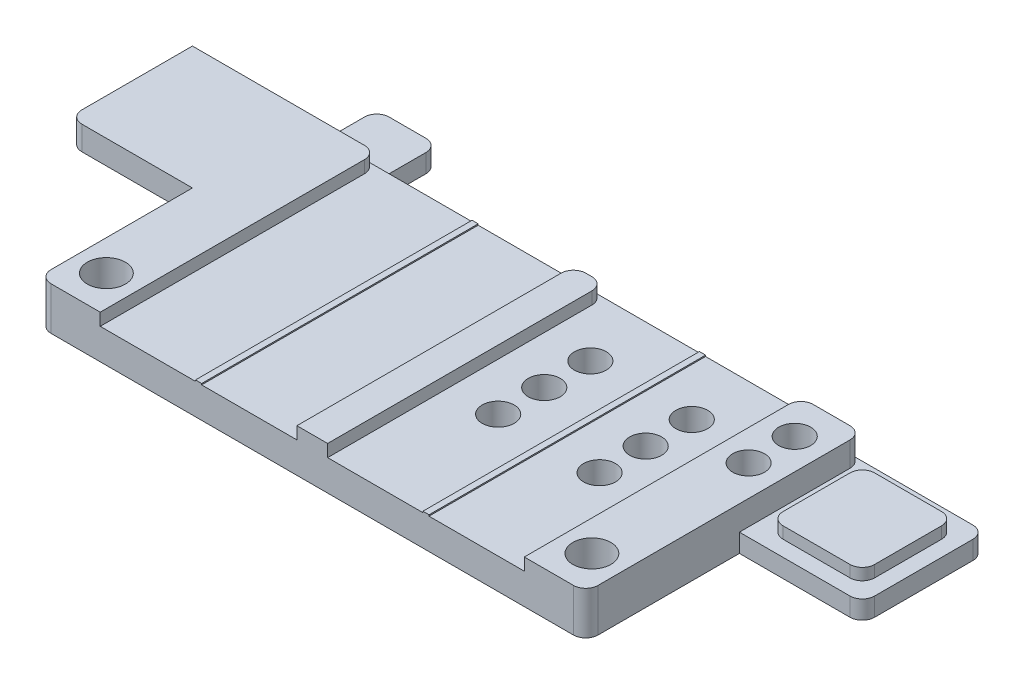
SolidWorks part; units mm, degrees
note: The reader was unsure of these and kept them because the rebuilt part matched: shared geometry of "Sketch1<3>", "Sketch1<4>", "Sketch5<3>", "Sketch5<4>", "Sketch5<5>".
ref_plane "Front Plane" through (0, 0, 0) normal (0, 0, 1) x (1, 0, 0)
ref_plane "Top Plane" through (0, 0, 0) normal (0, 1, 0) x (1, 0, 0)
ref_plane "Right Plane" through (0, 0, 0) normal (1, 0, 0) x (0, 0, -1)
sketch "Sketch1" plane through (0, 0, 0) normal (0, 1, 0) x (1, 0, 0)
  line L0 (0, 108.5954) -> (0, -94.6715) construction
  line L1 (-125.0313, 0) -> (305.9503, 0) construction
  line L10 (134.5, 0) -> (134.5, 45)
  line L11 (134.5, 45) -> (119, 45)
  line L12 (119, 45) -> (119, 0)
  line L13 (119, 0) -> (134.5, 0)
  line L14 (119, 45) -> (118, 45)
  line L15 (118, 45) -> (118, 0)
  line L16 (118, 0) -> (119, 0)
  line L18 (118, 45) -> (102.5, 45)
  line L22 (100, 108.5954) -> (100, 0) construction
  line L23 (102.5, 45) -> (102.5, 0)
  line L24 (102.5, 0) -> (118, 0)
  line L25 (102.5, 45) -> (97.5, 45)
  line L26 (97.5, 45) -> (97.5, 0)
  line L27 (97.5, 0) -> (102.5, 0)
  line L28 (97.5, 45) -> (82, 45)
  line L29 (82, 45) -> (82, 0)
  line L30 (82, 0) -> (97.5, 0)
  line L31 (82, 45) -> (81, 45)
  line L32 (81, 45) -> (81, 0)
  line L33 (81, 0) -> (82, 0)
  line L34 (81, 45) -> (65.5, 45)
  line L35 (65.5, 45) -> (65.5, 0)
  line L36 (65.5, 0) -> (81, 0)
  line L37 (134.5, 45) -> (144.5, 45)
  line L38 (144.5, 45) -> (144.5, 0)
  line L39 (144.5, 0) -> (134.5, 0)
  line L40 (65.5, 45) -> (55.5, 45)
  line L41 (55.5, 45) -> (55.5, 0)
  line L42 (55.5, 0) -> (65.5, 0)
  circle A10 centre (110.25, 35) radius 2.6
  circle A11 centre (110.25, 27.5) radius 2.6
  circle A12 centre (110.25, 20) radius 2.6
  circle A13 centre (126.75, 35) radius 2.6
  circle A14 centre (126.75, 27.5) radius 2.6
  circle A15 centre (126.75, 20) radius 2.6
  circle A16 centre (139.5, 39) radius 2.6
  circle A17 centre (139.5, 31.5) radius 2.6
  point P7 (100, 45)
  point P38 (110.25, 45)
  point P44 (126.75, 45)
  point P46 (139.5, 45)
  dimension "D6" = 5
  dimension "D7" = 15.5
  dimension "D8" = 1
  dimension "D9" = 15.5
  dimension "D12" = 7.5
  dimension "D14" = 10
  dimension "D10" = 5.2
  dimension "D13" = 7.5
  dimension "D15" = 7.5
  dimension "D16" = 10
  dimension "D2" = 45
  dimension "D3" = 15.5
  dimension "D4" = 1
  dimension "D5" = 15.5
  dimension "D11" = 100
  dimension "D17" = 6
  dimension "D18" = 10
extrude "Boss-Extrude1" add sketch "Sketch1" along normal blind 5 contours L35 L36 L32 L34 | L29 L30 L26 L28 | L23 L24 L15 L18 A12 A11 A10 | L12 L13 L10 L11 A15 A14 A13
extrude "Boss-Extrude2" add sketch "Sketch1<3>" along normal blind 5.2 contours L32 L33 L29 L31 | L15 L16 L12 L14
sketch "Sketch1<3>" plane through (0, 0, 0) normal (0, 1, 0) x (1, 0, 0) same geometry as "Sketch1"
extrude "Boss-Extrude3" add sketch "Sketch1<4>" along normal blind 7 contours L26 L27 L23 L25 | L39 L38 L37 L10 A17 A16 | L41 L42 L35 L40
sketch "Sketch1<4>" plane through (0, 0, 0) normal (0, 1, 0) x (1, 0, 0) same geometry as "Sketch1"
sketch "Sketch2" plane through (0, 0, 0) normal (0, -1, 0) x (-1, 0, 0)
  line L0 (-139.5, 31.5) -> (-139.5, 39) construction
  line L1 (-135.75, 42.75) -> (-143.25, 42.75)
  line L2 (-135.75, 42.75) -> (-135.75, 27.75)
  line L3 (-135.75, 27.75) -> (-143.25, 27.75)
  line L4 (-143.25, 42.75) -> (-143.25, 27.75)
  line L5 (-135.75, 42.75) -> (-143.25, 27.75) construction
  line L6 (-135.75, 27.75) -> (-143.25, 42.75) construction
  point P0 (-139.5, 35.25)
  dimension "D1" = 7.5
  dimension "D2" = 15
extrude "Cut-Extrude1" cut sketch "Sketch2" against normal blind 1.1
sketch "Sketch3" plane through (0, 7, 0) normal (0, 1, 0) x (1, 0, 0)
  line L0 (100, 49.6455) -> (100, -11.2034) construction
  line L2 (55.5, 0) -> (65.5, 0) construction
  line L3 (55.5, 45) -> (55.5, 0) construction
  circle A0 centre (60.5, 6) radius 3.1
  circle A1 centre (139.5, 6) radius 3.1
  point P9 (60.5, 0)
  dimension "D1" = 6.2
  dimension "D2" = 6
  dimension "D3" = 5
  dimension "D4" = 39.5
extrude "Cut-Extrude2" cut sketch "Sketch3" against normal through all
sketch "Sketch5" plane through (0, 0, 0) normal (0, 1, 0) x (1, 0, 0)
  line L0 (144.5, 25) -> (164.5, 25)
  line L1 (144.5, 45) -> (144.5, 0) construction
  line L2 (164.5, 25) -> (164.5, 45)
  line L3 (164.5, 45) -> (144.5, 45)
  line L4 (144.5, 45) -> (144.5, 25)
  line L5 (35.5, 25) -> (55.5, 25)
  line L6 (147.05, 42.45) -> (161.95, 42.45)
  line L7 (147.05, 42.45) -> (147.05, 27.55)
  line L8 (147.05, 27.55) -> (161.95, 27.55)
  line L9 (161.95, 42.45) -> (161.95, 27.55)
  line L10 (147.05, 42.45) -> (161.95, 27.55) construction
  line L11 (147.05, 27.55) -> (161.95, 42.45) construction
  line L12 (55.5, 25) -> (55.5, 45)
  line L13 (55.5, 45) -> (35.5, 45)
  line L14 (35.5, 45) -> (35.5, 25)
  line L15 (37.9, 42.6) -> (53.1, 42.6)
  line L16 (37.9, 42.6) -> (37.9, 27.4)
  line L17 (37.9, 27.4) -> (53.1, 27.4)
  line L18 (53.1, 42.6) -> (53.1, 27.4)
  line L19 (37.9, 42.6) -> (53.1, 27.4) construction
  line L20 (37.9, 27.4) -> (53.1, 42.6) construction
  point P5 (154.5, 35)
  point P13 (154.5, 45)
  point P15 (164.5, 35)
  point P19 (45.5, 35)
  point P25 (45.5, 45)
  point P26 (55.5, 35)
  line M28 (55.5, 0) -> (55.5, 45)
  line M30 (144.5, 45) -> (144.5, 0)
  dimension "D1" = 20
  dimension "D2" = 20
  dimension "D3" = 14.9
  dimension "D4" = 14.9
  dimension "D5" = 20
  dimension "D6" = 20
  dimension "D7" = 15.2
  dimension "D8" = 15.2
extrude "Boss-Extrude4" add sketch "Sketch5" along normal blind 3 contours L3 L2 L0 L9 L6 L7 L8 M30 | L6 L9 L8 L7
extrude "Boss-Extrude5" add sketch "Sketch5<3>" along normal blind 4.9 contours L6 L9 L8 L7
sketch "Sketch5<3>" plane through (0, 0, 0) normal (0, 1, 0) x (1, 0, 0) same geometry as "Sketch5"
extrude "Boss-Extrude6" add sketch "Sketch5<4>" against normal blind 3.9 from surface at 7 contours L14 L13 L5 L18 L15 L16 L17 M28 starting at face at (60.5, 7, -2.9)
sketch "Sketch5<4>" plane through (0, 0, 0) normal (0, 1, 0) x (1, 0, 0) same geometry as "Sketch5"
extrude "Boss-Extrude7" add sketch "Sketch5<5>" against normal blind 1 from surface at 7 contours L15 L18 L17 L16 starting at face at (60.5, 7, -2.9)
sketch "Sketch5<5>" plane through (0, 0, 0) normal (0, 1, 0) x (1, 0, 0) same geometry as "Sketch5"
fillet "Fillet1" radius 2 4 edges at (147.05, 3.95, -27.55) (147.05, 3.95, -42.45) (161.95, 3.95, -42.45) (161.95, 3.95, -27.55)
sketch "Sketch6" plane through (0, 7, 0) normal (0, 1, 0) x (1, 0, 0)
  line L0 (65.5, 45) -> (65.5, 55)
  line L1 (65.5, 55) -> (55.5, 55)
  line L2 (55.5, 55) -> (55.5, 45)
  line L3 (65.5, 45) -> (35.5, 45) construction
  line L4 (55.5, 45) -> (65.5, 45)
  dimension "D1" = 10
  dimension "D2" = 10
extrude "Boss-Extrude8" add sketch "Sketch6" along normal blind 3 from surface at -7 starting at face at (60.5, 0, -2.9)
fillet "Fillet3" radius 2 12 edges at (35.5, 5.05, -25) (164.5, 1.5, -25) (144.5, 3.5, 0) (55.5, 3.5, 0) (65.5, 1.5, -55) (65.5, 6, -45) (134.5, 6, -45) (144.5, 5, -45) (97.5, 6, -45) (102.5, 6, -45) (55.5, 1.5, -55) (164.5, 1.5, -45)
chamfer "Chamfer1" distance 1 angle 45 1 edges at (45.5, 3.1, -45)
